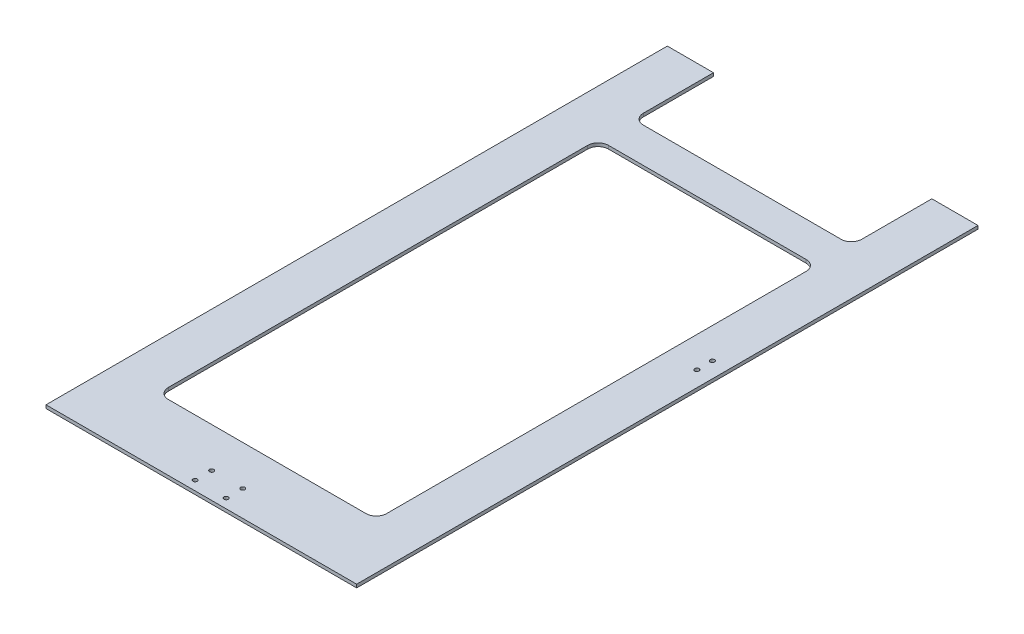
SolidWorks part; units mm, degrees
ref_plane "Front Plane" through (0, 0, 0) normal (0, 0, 1) x (1, 0, 0)
ref_plane "Top Plane" through (0, 0, 0) normal (0, 1, 0) x (1, 0, 0)
ref_plane "Right Plane" through (0, 0, 0) normal (1, 0, 0) x (0, 0, -1)
sketch "Sketch1" plane through (0, 0, 0) normal (0, 1, 0) x (1, 0, 0)
  line L1 (150, -300) -> (-150, -300)
  line L2 (150, -300) -> (150, 300)
  line L3 (150, 300) -> (-150, 300)
  line L4 (-150, -300) -> (-150, 300)
  line L5 (150, -300) -> (-150, 300) construction
  line L6 (150, 300) -> (-150, -300) construction
  point P0 (0, 0)
  dimension "D1" = 600
  dimension "D2" = 300
extrude "Boss-Extrude1" add sketch "Sketch1" along normal blind 3.175
sketch "Sketch3" plane through (0, 3.175, 0) normal (0, 1, 0) x (1, 0, 0)
  line L0 (-95.4457, -236.4845) -> (95.4457, -236.4845)
  line L1 (0, 300) -> (0, -300) construction
  line L2 (105.4457, -226.4845) -> (105.4457, 178.5785)
  line L3 (95.4457, 188.5785) -> (-95.4457, 188.5785)
  line L4 (105.4457, 338.7705) -> (105.4457, 232.3181)
  line L5 (150, 300) -> (-150, 300) construction
  line L6 (95.4457, 222.3181) -> (-95.4457, 222.3181)
  line L7 (95.4457, 348.7705) -> (-95.4457, 348.7705)
  line L8 (0, -300) -> (0, -342.0806) construction
  line L9 (-105.4457, 338.7705) -> (-105.4457, 232.3181)
  line L10 (-105.4457, -226.4845) -> (-105.4457, 178.5785)
  arc A0 (-105.4457, 338.7705) -> (-95.4457, 348.7705) centre (-95.4457, 338.7705) cw
  arc A1 (-105.4457, 232.3181) -> (-95.4457, 222.3181) centre (-95.4457, 232.3181) ccw
  arc A2 (105.4457, 338.7705) -> (95.4457, 348.7705) centre (95.4457, 338.7705) ccw
  arc A3 (105.4457, 232.3181) -> (95.4457, 222.3181) centre (95.4457, 232.3181) cw
  arc A4 (105.4457, 178.5785) -> (95.4457, 188.5785) centre (95.4457, 178.5785) ccw
  arc A5 (-105.4457, 178.5785) -> (-95.4457, 188.5785) centre (-95.4457, 178.5785) cw
  arc A6 (-105.4457, -226.4845) -> (-95.4457, -236.4845) centre (-95.4457, -226.4845) ccw
  arc A7 (95.4457, -236.4845) -> (105.4457, -226.4845) centre (95.4457, -226.4845) ccw
  point P17 (0, 300)
  point P18 (0, 222.3181)
  point P19 (0, 188.5785)
  point P20 (0, -236.4845)
  point P22 (-105.4457, 300)
  point P25 (-105.4457, 222.3181)
  point P28 (105.4457, 300)
  point P31 (105.4457, 222.3181)
  point P34 (105.4457, 188.5785)
  point P37 (-105.4457, 188.5785)
  point P40 (-105.4457, -236.4845)
  point P43 (105.4457, -236.4845)
  point P44 (0, 300)
  dimension "D1" = 10
extrude "Cut-Extrude1" cut sketch "Sketch3" against normal blind 10
sketch "Sketch4" plane through (0, 3.175, 0) normal (0, 1, 0) x (1, 0, 0)
  circle A0 centre (15, -291) radius 2.05
  circle A1 centre (-15, -291) radius 2.05
  circle A2 centre (-15, -275) radius 2.05
  circle A3 centre (15, -275) radius 2.05
  dimension "D1" = 4.1
extrude "Cut-Extrude2" cut sketch "Sketch4" against normal blind 51
sketch "Sketch5" plane through (0, 3.175, 0) normal (0, 1, 0) x (1, 0, 0)
  circle A0 centre (135, 43.495) radius 2.1
  circle A1 centre (135, 58.495) radius 2.1
  dimension "D1" = 4.2
extrude "Cut-Extrude3" cut sketch "Sketch5" against normal blind 67
